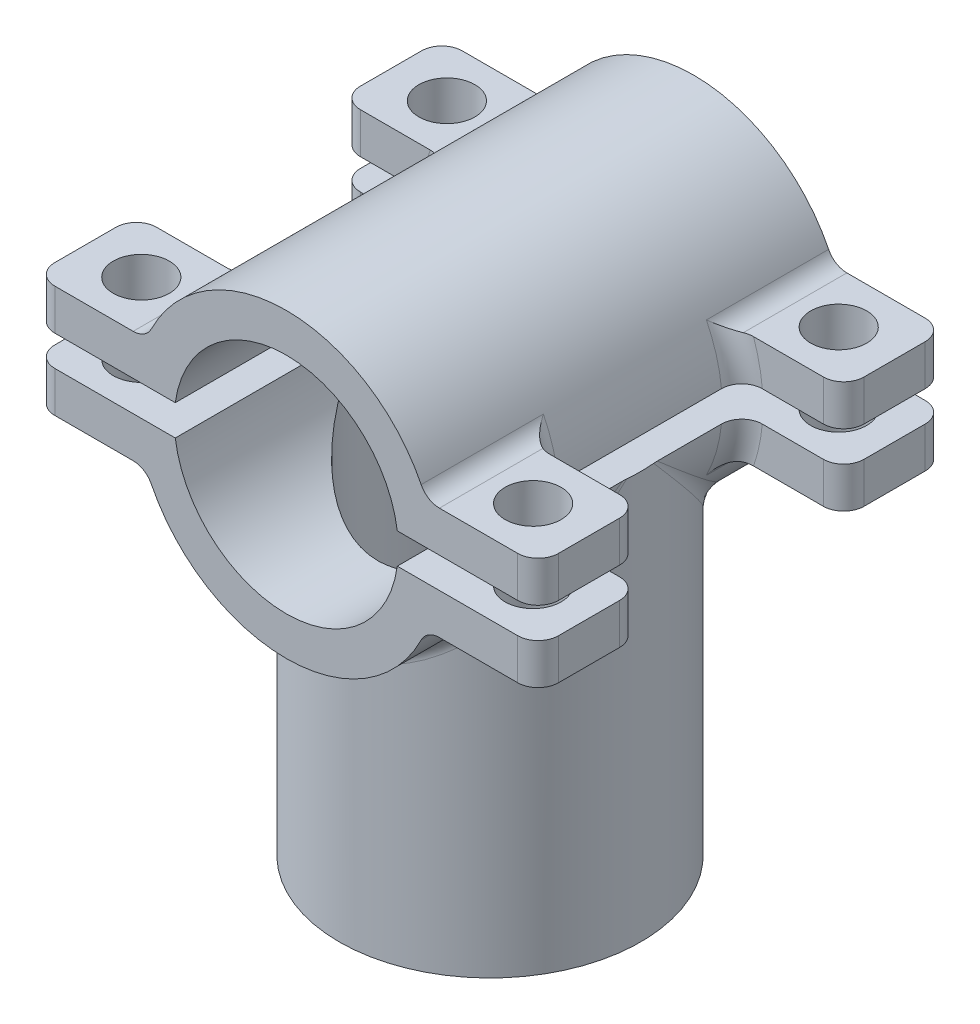
SolidWorks part; units mm, degrees
ref_plane "Front Plane" through (0, 0, 0) normal (0, 0, 1) x (1, 0, 0)
ref_plane "Top Plane" through (0, 0, 0) normal (0, 1, 0) x (1, 0, 0)
ref_plane "Right Plane" through (0, 0, 0) normal (1, 0, 0) x (0, 0, -1)
sketch "Sketch1" plane through (0, 0, 0) normal (0, 0, 1) x (1, 0, 0)
  line L0 (-13.8908, 0) -> (13.8908, 0) construction
  line L1 (0, 0) -> (0, 1.5) construction
  line L5 (-14.7238, 1.5) -> (14.7238, 1.5) construction
  line L8 (14.7238, 1.5) -> (10.8972, 1.5)
  line L9 (-10.8972, 1.5) -> (-14.7238, 1.5)
  arc A6 (10.8972, 1.5) -> (-10.8972, 1.5) centre (0, 0) ccw
  arc A7 (14.7238, 1.5) -> (-14.7238, 1.5) centre (0, 0) ccw
  point P3 (0, 0)
  dimension "D2" = 14.8
  dimension "D1" = 11
  dimension "D4" = 1.5
extrude "Boss-Extrude2" add sketch "Sketch1" along normal blind 40
sketch "Sketch3" plane through (0, 0, 0) normal (0, 0, 1) x (1, 0, 0)
  line L0 (-14.7238, 1.5) -> (-12.7238, 1.5)
  line L1 (-14.7238, 1.5) -> (-10.8972, 1.5) construction
  line L2 (-12.7238, 1.5) -> (-12.7238, 5.5)
  line L3 (-14.7238, 1.5) -> (-24.7238, 1.5)
  line L4 (-24.7238, 1.5) -> (-24.7238, 5.5)
  line L5 (-24.7238, 5.5) -> (-12.7238, 5.5)
  line L6 (14.7238, 1.5) -> (12.7238, 1.5)
  line L7 (10.8972, 1.5) -> (14.7238, 1.5) construction
  line L8 (12.7238, 1.5) -> (12.7238, 5.5)
  line L9 (14.7238, 1.5) -> (24.7238, 1.5)
  line L10 (24.7238, 1.5) -> (24.7238, 5.5)
  line L11 (24.7238, 5.5) -> (12.7238, 5.5)
  dimension "D1" = 4
  dimension "D2" = 10
  dimension "D3" = 2
  dimension "D4" = 10
  dimension "D5" = 2
  dimension "D6" = 4
extrude "Boss-Extrude3" add sketch "Sketch3" along normal blind 10
extrude "Boss-Extrude4" add sketch "Sketch3<2>" against normal blind 10 from surface starting at face at (0, 7.2, 40)
sketch "Sketch3<2>" plane through (0, 0, 0) normal (0, 0, 1) x (1, 0, 0) same geometry as "Sketch3"
sketch "Sketch4" plane through (0, 0, 0) normal (0, 1, 0) x (1, 0, 0)
  line L0 (-19.2319, 0) -> (-19.2319, -10) construction
  line L1 (-13.7401, 0) -> (-24.7238, 0) construction
  line L2 (-13.7401, -10) -> (-24.7238, -10) construction
  line L3 (-24.7238, -5) -> (-13.7401, -5) construction
  line L4 (-24.7238, -10) -> (-24.7238, 0) construction
  line L5 (-13.7401, -10) -> (-13.7401, 0) construction
  line L6 (-19.2319, -30) -> (-19.2319, -40) construction
  line L7 (-24.7238, -30) -> (-13.7401, -30) construction
  line L8 (-24.7238, -40) -> (-13.7401, -40) construction
  line L9 (-24.7238, -35) -> (-13.7401, -35) construction
  line L10 (-24.7238, -30) -> (-24.7238, -40) construction
  line L11 (-13.7401, -40) -> (-13.7401, -30) construction
  line L12 (19.2319, -10) -> (19.2319, 0) construction
  line L13 (24.7238, -10) -> (13.7401, -10) construction
  line L14 (24.7238, 0) -> (13.7401, 0) construction
  line L15 (13.7401, -5) -> (24.7238, -5) construction
  line L16 (13.7401, 0) -> (13.7401, -10) construction
  line L17 (24.7238, -10) -> (24.7238, 0) construction
  line L18 (19.2319, -30) -> (19.2319, -40) construction
  line L19 (13.7401, -30) -> (24.7238, -30) construction
  line L20 (13.7401, -40) -> (24.7238, -40) construction
  line L21 (13.7401, -35) -> (24.7238, -35) construction
  line L22 (13.7401, -30) -> (13.7401, -40) construction
  line L23 (24.7238, -30) -> (24.7238, -40) construction
  circle A0 centre (-19.2319, -5) radius 2.75
  circle A1 centre (19.2319, -5) radius 2.75
  circle A2 centre (-19.2319, -35) radius 2.75
  circle A3 centre (19.2319, -35) radius 2.75
  dimension "D1" = 5.5
extrude "Cut-Extrude1" cut sketch "Sketch4" along normal through all both and the other way through all
fillet "Fillet1" radius 2 16 edges at (14.3718, 3.5344, 10) (13.7401, 5.5, 5) (24.7238, 3.5, 0) (24.7238, 3.5, 10) (14.3718, 3.5344, 30) (13.7401, 5.5, 35) (24.7238, 3.5, 30) (24.7238, 3.5, 40) (-14.3718, 3.5344, 10) (-13.7401, 5.5, 5) (-24.7238, 3.5, 0) (-24.7238, 3.5, 10) (-24.7238, 3.5, 30) (-14.3718, 3.5344, 30) (-13.7401, 5.5, 35) (-24.7238, 3.5, 40)
mirror "Mirror2" about plane through (0, 0, 0) normal (0, 1, 0) of bodies 106
ref_plane "Plane1" through (0, -1.5, 0) normal (0, 1, 0) x (1, 0, 0)
sketch "Sketch5" plane through (0, -1.5, 0) normal (0, 1, 0) x (1, 0, 0)
  line L0 (0, -40) -> (0, 0) construction
  line L1 (-13.2433, -40) -> (13.2433, -40) construction
  line L2 (-14.7238, -20) -> (14.7238, -20) construction
  line L3 (-14.7238, -28) -> (-14.7238, -12) construction
  line L4 (14.7238, -28) -> (14.7238, -12) construction
  line L5 (0, -20) -> (0, -21.5) construction
  line L6 (0, -20) -> (0, -18.5) construction
  circle A1 centre (0, -20) radius 14.8
  circle A2 centre (0, -20) radius 11
  point P14 (0, 0)
  dimension "D1" = 22
  dimension "D2" = 29.6
extrude "Boss-Extrude6" add sketch "Sketch5" against normal blind 40
sketch "Sketch6" plane through (0, 0, 0) normal (0, 0, 1) x (1, 0, 0)
  line L1 (10.8972, -1.5) -> (-10.8972, -1.5)
  line L2 (10.8972, -1.5) -> (-10.8972, -1.5)
  arc A1 (-10.8972, -1.5) -> (10.8972, -1.5) centre (0, 0) ccw
  arc A2 (-10.8972, -1.5) -> (10.8972, -1.5) centre (0, 0) ccw
  dimension "D1" = 0
extrude "Cut-Extrude2" cut sketch "Sketch6" along normal through all both and the other way through all
sketch "Sketch7" plane through (0, -1.5, 0) normal (0, 1, 0) x (1, 0, 0)
  circle A1 centre (0, -20) radius 11
  circle A2 centre (0, -20) radius 11
  dimension "D1" = 0
extrude "Cut-Extrude4" cut sketch "Sketch7" against normal blind 45
sketch "Sketch8" plane through (0, 0, 0) normal (0, 0, 1) x (1, 0, 0)
  line L0 (0, -41.5) -> (0, -31.5) construction
  line L1 (-14.8, -41.5) -> (14.8, -41.5) construction
  circle A0 centre (0, -31.5) radius 2
  dimension "D2" = 4
  dimension "D1" = 10
extrude "Cut-Extrude5" cut sketch "Sketch8" along normal up to surface (9.1833 mm away) up to face at (0, -41.5, 31)
fillet "Fillet2" radius 2 2 edges at (0, -14.8, 5.2) (0, -14.8, 34.8)
